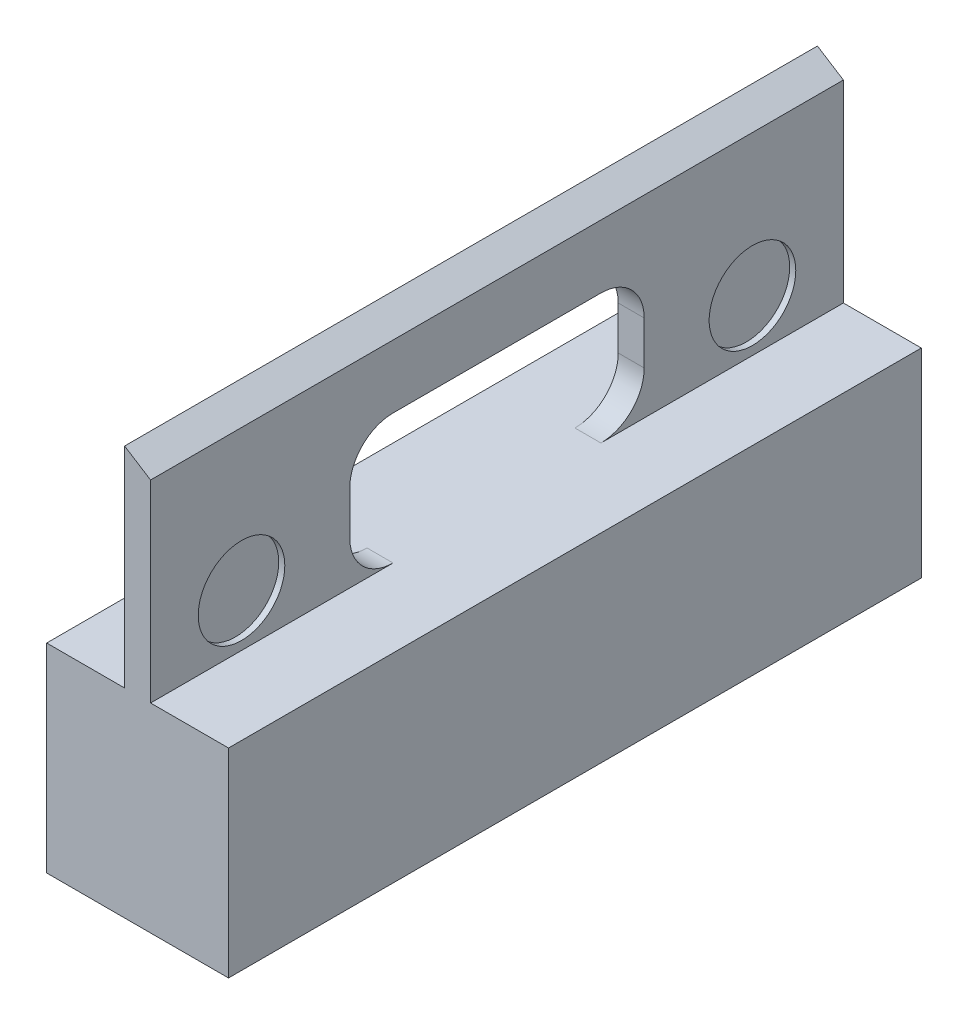
SolidWorks part; units mm, degrees
ref_plane "Plan de face" through (0, 0, 0) normal (0, 0, 1) x (1, 0, 0)
ref_plane "Plan de dessus" through (0, 0, 0) normal (0, 1, 0) x (1, 0, 0)
ref_plane "Plan de droite" through (0, 0, 0) normal (1, 0, 0) x (0, 0, -1)
sketch "Esquisse1" plane through (0, 0, 0) normal (0, 1, 0) x (1, 0, 0)
  line L1 (0, 0) -> (-21, 0)
  line L2 (0, 0) -> (0, -80)
  line L3 (0, -80) -> (-21, -80)
  line L4 (-21, 0) -> (-21, -80)
  dimension "D1" = 80
  dimension "D2" = 21
extrude "Boss.-Extru.1" add sketch "Esquisse1" along normal blind 2 and the other way blind 21
sketch "Esquisse10" plane through (0, 2, 0) normal (0, 1, 0) x (1, 0, 0)
  line L0 (0, 0) -> (-21, 0) construction
  line L1 (-9, 0) -> (-12, 0)
  line L2 (-9, 0) -> (-9, -80)
  line L3 (-9, -80) -> (-12, -80)
  line L4 (-12, 0) -> (-12, -80)
  line L5 (-21, -80) -> (0, -80) construction
  line L6 (0, -80) -> (0, 0) construction
  dimension "D1" = 9
  dimension "D2" = 3
extrude "Boss.-Extru.2" add sketch "Esquisse10" along normal blind 24.2
sketch "Esquisse11" plane through (-12, 0, 0) normal (-1, 0, 0) x (0, 0, 1)
  line L0 (0, 2) -> (80, 2) construction
  line L1 (57, 2) -> (23, 2)
  line L2 (57, 2) -> (57, 17)
  line L3 (57, 17) -> (23, 17)
  line L4 (23, 2) -> (23, 17)
  line L5 (0, 26.2) -> (0, 2) construction
  line L6 (80, 26.2) -> (80, 2) construction
  dimension "D1" = 23
  dimension "D2" = 23
  dimension "D3" = 15
extrude "Enlèv. mat.-Extru.1" cut sketch "Esquisse11" against normal blind 3
fillet "Congé1" radius 5 4 edges at (-10.5, 2, 23) (-10.5, 17, 23) (-10.5, 17, 57) (-10.5, 2, 57)
sketch "Esquisse12" plane through (-9, 0, 0) normal (1, 0, 0) x (0, 0, -1)
  line L0 (0, 26.2) -> (0, 2) construction
  line L1 (-80, 26.2) -> (-80, 2) construction
  line L3 (-80, 2) -> (-52, 2) construction
  line L4 (-28, 2) -> (0, 2) construction
  circle A0 centre (-69.5, 8) radius 5
  circle A1 centre (-10.5, 8) radius 5
  dimension "D1" = 10
  dimension "D2" = 10
  dimension "D3" = 10.5
  dimension "D4" = 10.5
  dimension "D5" = 6
  dimension "D6" = 6
sketch "Esquisse13" plane through (0, 0, 80) normal (0, 0, 1) x (1, 0, 0)
  line L0 (-12, 26.2) -> (-9, 26.2)
  line L1 (-9, 26.2) -> (-9, 24.3)
  line L2 (-9, 26.2) -> (-9, 2) construction
  line L3 (-9, 24.3) -> (-12, 26.2)
  dimension "D1" = 1.9
extrude "Enlèv. mat.-Extru.2" cut sketch "Esquisse13" against normal blind 81
shell "Coque2" thickness 2 removed face at (-10.5, -21, 40)
sketch "Esquisse15" plane through (-21, 0, 0) normal (-1, 0, 0) x (0, 0, 1)
  line L0 (0, -21) -> (80, -21) construction
  line L1 (48, -21) -> (32, -21)
  line L2 (48, -21) -> (48, -11)
  line L3 (48, -11) -> (32, -11)
  line L4 (32, -21) -> (32, -11)
  line L5 (0, -21) -> (0, 2) construction
  line L6 (80, -21) -> (80, 2) construction
  dimension "D1" = 32
  dimension "D2" = 32
  dimension "D3" = 10
extrude "Enlèv. mat.-Extru.3" cut sketch "Esquisse15" against normal blind 2
extrude "Enlèv. mat.-Extru.4" cut sketch "Esquisse12" against normal blind 0.7
